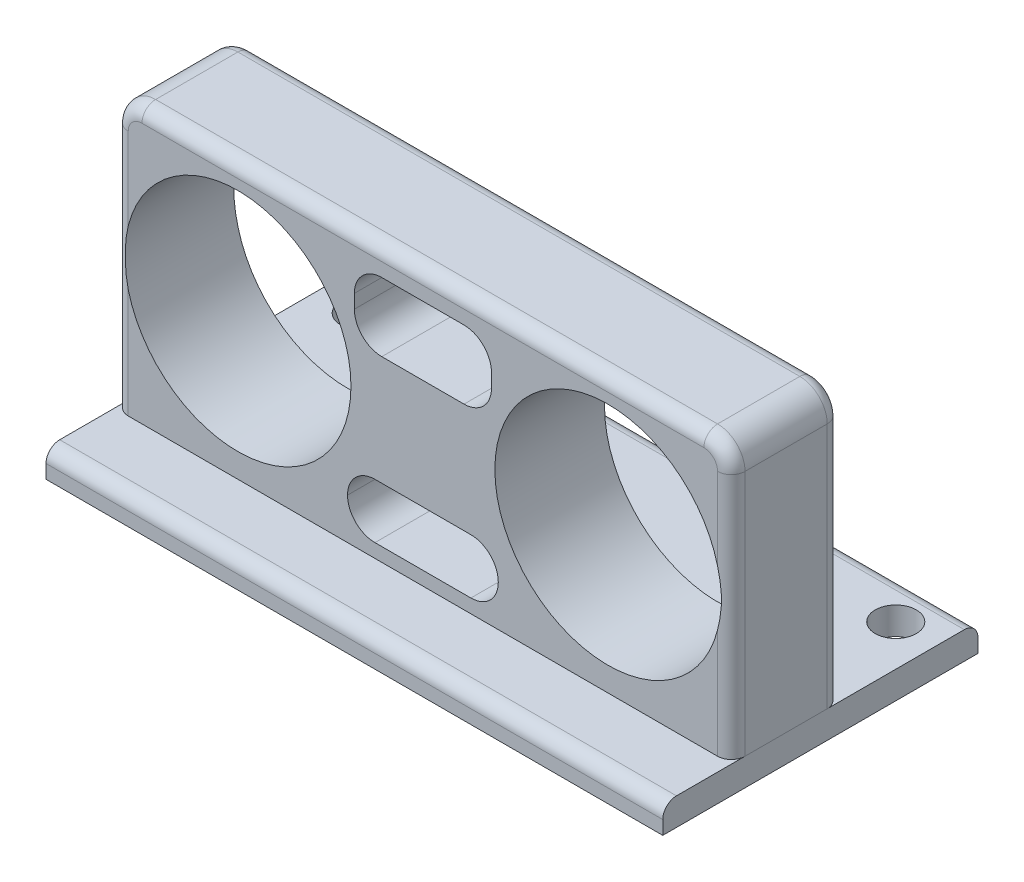
SolidWorks part; units mm, degrees
ref_plane "Alzado" through (0, 0, 0) normal (0, 0, 1) x (1, 0, 0)
ref_plane "Planta" through (0, 0, 0) normal (0, 1, 0) x (1, 0, 0)
ref_plane "Vista lateral" through (0, 0, 0) normal (1, 0, 0) x (0, 0, -1)
sketch "Croquis1" plane through (0, 0, 0) normal (0, 0, 1) x (1, 0, 0)
  line L0 (0, -10) -> (9, -10) construction
  line L1 (0, 0) -> (45, 0)
  line L2 (0, 0) -> (0, -20)
  line L3 (0, -20) -> (45, -20)
  line L4 (45, 0) -> (45, -20)
  line L5 (45, -10) -> (36, -10) construction
  circle A0 centre (9, -10) radius 8.25
  circle A1 centre (36, -10) radius 8.25
  dimension "D4" = 16.5
  dimension "D6" = 16.5
  dimension "D1" = 45
  dimension "D2" = 20
  dimension "D3" = 9
  dimension "D5" = 9
extrude "Saliente-Extruir1" add sketch "Croquis1" along normal blind 8
sketch "Croquis2" plane through (0, -20, 0) normal (0, -1, 0) x (-1, 0, 0)
  line L0 (0, -2) -> (-45, -2) construction
  line L1 (0, -8) -> (0, 0) construction
  line L2 (-45, -8) -> (-45, 0) construction
  line L3 (0, 0) -> (-45, 0) construction
  line L5 (-45, -13) -> (0, -13)
  line L6 (-45, -13) -> (-45, 10)
  line L7 (-45, 10) -> (0, 10)
  line L8 (0, -13) -> (0, 10)
  line L9 (0, -8) -> (-45, -8) construction
  line L10 (0, -6) -> (-45, -6) construction
  dimension "D1" = 2
  dimension "D2" = 12
  dimension "D3" = 2
  dimension "D4" = 7
  dimension "D5" = 45
extrude "Saliente-Extruir2" add sketch "Croquis2" along normal blind 2 separate body
sketch "Croquis4" plane through (0, 0, 0) normal (0, 0, -1) x (-1, 0, 0)
  line L0 (-22.5, 0) -> (-22.5, -20) construction
  line L1 (-45, 0) -> (0, 0) construction
  line L2 (0, -20) -> (-45, -20) construction
  line L3 (-45, 0) -> (0, 0) construction
  line L4 (-28, -15) -> (-17, -15)
  line L5 (-28, -15) -> (-28, -19)
  line L6 (-28, -19) -> (-17, -19)
  line L7 (-17, -15) -> (-17, -19)
  line L9 (-17.5, -7) -> (-17.5, -2)
  line L10 (-27.5, -2) -> (-17.5, -2)
  line L11 (-27.5, -7) -> (-27.5, -2)
  line L12 (-27.5, -7) -> (-17.5, -7)
  dimension "D1" = 11
  dimension "D2" = 5.5
  dimension "D3" = 4
  dimension "D4" = 15
  dimension "D5" = 2
  dimension "D6" = 5
  dimension "D7" = 10
  dimension "D8" = 5
  dimension "D9" = 90
  dimension "D10" = 90
extrude "Cortar-Extruir3" cut sketch "Croquis4" against normal through all
sketch "Croquis5" plane through (0, -20, 0) normal (0, 1, 0) x (1, 0, 0)
  line L0 (0, 10) -> (45, 10) construction
  line L1 (0, -13) -> (0, 10) construction
  line L2 (45, 10) -> (45, -13) construction
  circle A0 centre (3, 7) radius 1.5
  circle A1 centre (42, 7) radius 1.5
  dimension "D1" = 3
  dimension "D2" = 3
  dimension "D4" = 3
  dimension "D5" = 3
  dimension "D6" = 3
  dimension "D3" = 3
extrude "Cortar-Extruir4" cut sketch "Croquis5" against normal through all
fillet "Redondeo1" radius 2 4 edges at (17, -19, 4) (28, -15, 4) (17, -15, 4) (28, -19, 4)
fillet "Redondeo2" radius 2 6 edges at (45, 0, 4) (0, 0, 4) (27.5, -7, 4) (27.5, -2, 4) (17.5, -2, 4) (17.5, -7, 4)
fillet "Redondeo3" radius 1 10 edges at (45, -11, 8) (44.4142, -0.5858, 8) (0, -11, 8) (0.5858, -0.5858, 8) (45, -11, 0) (44.4142, -0.5858, 0) (0, -11, 0) (0.5858, -0.5858, 0) (22.5, 0, 8) (22.5, 0, 0)
fillet "Redondeo5" radius 1 2 edges at (22.5, -20, -10) (22.5, -20, 13)
